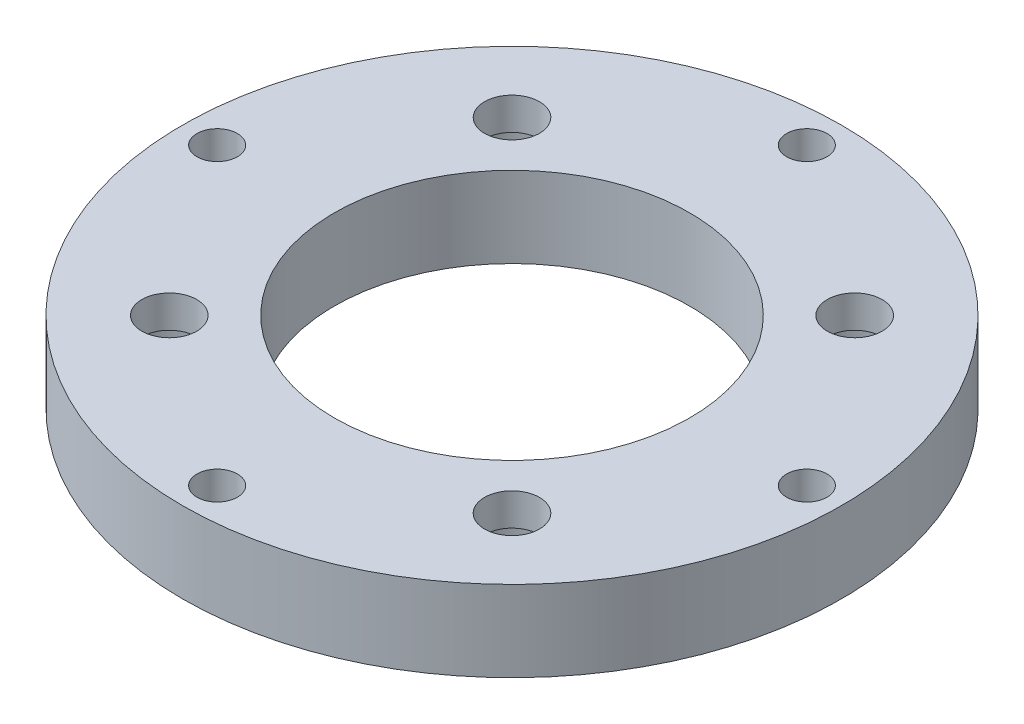
SolidWorks part; units mm, degrees
material "3.1355 (EN-AW 2024)"
ref_plane "Front" through (0, 0, 0) normal (0, 0, 1) x (1, 0, 0)
ref_plane "Top" through (0, 0, 0) normal (0, 1, 0) x (1, 0, 0)
ref_plane "Right" through (0, 0, 0) normal (1, 0, 0) x (0, 0, -1)
sketch "Эскиз1" plane through (0, 0, 0) normal (0, 1, 0) x (1, 0, 0)
  circle A0 centre (0, 0) radius 20.4
  circle A1 centre (0, 0) radius 11
  dimension "D1" = 40.8
  dimension "D2" = 22
extrude "Бобышка-Вытянуть1" add sketch "Эскиз1" along normal blind 5
sketch "Эскиз2" plane through (0, 5, 0) normal (0, 1, 0) x (1, 0, 0)
  circle A0 centre (0, 0) radius 18.25 construction
  point P3 (0, 18.25)
  point P4 (18.25, 0)
  point P5 (0, -18.25)
  point P6 (-18.25, 0)
  dimension "D1" = 36.5
hole_wizard "Отверстие обработанное метчиком M3x0.51" positions "Эскиз5" profile "Эскиз4" tap size "M3x0.5" standard "Ansi Metric" end condition through all
sketch "Эскиз5" plane through (0, 5, 0) normal (0, 1, 0) x (1, 0, 0)
  point P0 (-18.25, 0)
  point P3 (0, 18.25)
  point P6 (18.25, 0)
  point P9 (0, -18.25)
sketch "Эскиз4" plane through (-18.25, 5, 0) normal (1, 0, 0) x (0, 0, 1)
  line L0 (0, 0) -> (0, 5)
  line L1 (0, 5) -> (1.25, 5)
  line L2 (1.25, 5) -> (1.25, 0)
  line L5 (1.25, 0) -> (0, 0)
  line L11 (0, -6.35) -> (0, 107.95) construction
  dimension "Диаметр проходного сверла" = 2.5
  dimension "Глубина проходного сверла" = 5
cosmetic thread "Отверстие резьбы1" parameters "D2"=3
cosmetic thread "Отверстие резьбы2" parameters "D2"=3
cosmetic thread "Отверстие резьбы3" parameters "D2"=3
cosmetic thread "Отверстие резьбы4" parameters "D2"=3
sketch "Эскиз6" plane through (0, 0, 0) normal (0, -1, 0) x (1, 0, 0)
  line L0 (0, 0) -> (-10.6066, 10.6066) construction
  line L1 (0, 0) -> (-15, 0) construction
  line L2 (0, 0) -> (10.6066, 10.6066) construction
  line L3 (0, 0) -> (10.6066, -10.6066) construction
  line L4 (0, 0) -> (-10.6066, -10.6066) construction
  circle A0 centre (0, 0) radius 15 construction
  point P11 (0, 0)
  dimension "D1" = 30
  dimension "D2" = 45
  dimension "D3" = 4
hole_wizard "Цековка для винта с внутренним шестигранником M31" positions "Эскиз8" profile "Эскиз7" counterbore size "M3" standard "Ansi Metric" end condition through all
sketch "Эскиз8" plane through (0, 0, 0) normal (0, -1, 0) x (-1, 0, 0)
  point P0 (10.6066, -10.6066)
  point P3 (-10.6066, -10.6066)
  point P6 (-10.6066, 10.6066)
  point P9 (10.6066, 10.6066)
sketch "Эскиз7" plane through (-10.6066, 0, 10.6066) normal (1, 0, 0) x (0, 0, -1)
  line L0 (0, 0) -> (0, 5)
  line L1 (0, 5) -> (1.7, 5)
  line L3 (1.7, 5) -> (1.7, 3)
  line L4 (1.7, 3) -> (3.25, 3)
  line L5 (3.25, 3) -> (3.25, 0)
  line L7 (3.25, 0) -> (0, 0)
  line L11 (0, -6.35) -> (0, 107.95) construction
  dimension "Диаметр сквозного отверстия" = 3.4
  dimension "Глубина сквозного отверстия" = 5
  dimension "Диаметр цековки" = 6.5
  dimension "Глубина цековки" = 3
equation "\"D1@Эскиз2\"=36.5"
